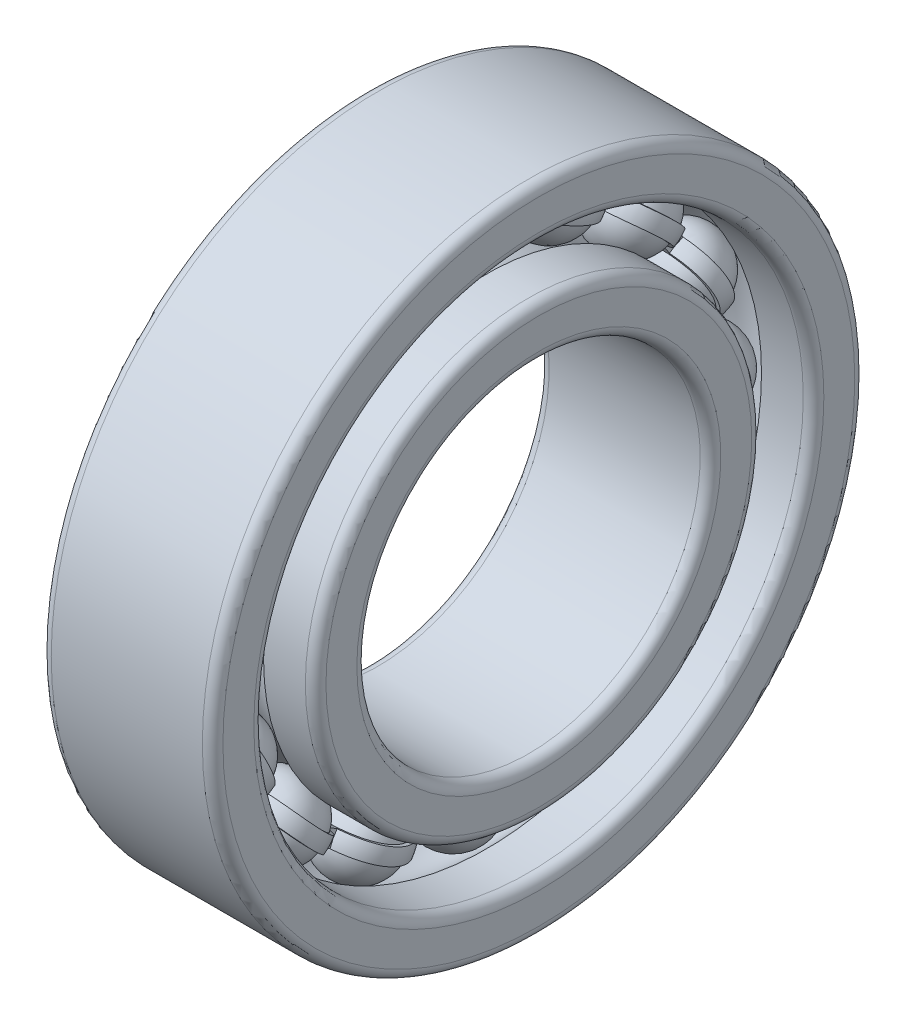
SolidWorks part; units mm, degrees
material "AISI 304"
ref_plane "前视基准面" through (0, 0, 0) normal (0, 0, 1) x (1, 0, 0)
ref_plane "上视基准面" through (0, 0, 0) normal (0, 1, 0) x (1, 0, 0)
ref_plane "右视基准面" through (0, 0, 0) normal (1, 0, 0) x (0, 0, -1)
sketch "尺寸草图" plane through (0, 0, 0) normal (0, 0, 1) x (1, 0, 0)
  line L0 (-19.9271, 0) -> (19.9271, 0) construction
  line L1 (0, 21.603) -> (0, -21.603) construction
  line L2 (-2.2, 9.5) -> (2.2, 9.5)
  line L3 (2.5, 9.2) -> (2.5, 8.3)
  line L4 (-2.5, 9.2) -> (-2.5, 8.3)
  line L5 (-2.2, 8) -> (2.2, 8)
  line L6 (-3.5, 7.25) -> (3.3577, 7.25) construction
  line L7 (-2.2, 6.5) -> (2.2, 6.5)
  line L8 (2.5, 6.2) -> (2.5, 5.3)
  line L9 (2.2, 5) -> (-2.2, 5)
  line L10 (-2.5, 5.3) -> (-2.5, 6.2)
  line L11 (0, 7.25) -> (0, 8.375) construction
  circle A0 centre (0, 7.25) radius 1.125
  arc A1 (2.5, 8.3) -> (2.2, 8) centre (2.2, 8.3) cw
  arc A2 (2.5, 6.2) -> (2.2, 6.5) centre (2.2, 6.2) ccw
  arc A3 (-2.2, 6.5) -> (-2.5, 6.2) centre (-2.2, 6.2) ccw
  arc A4 (-2.2, 8) -> (-2.5, 8.3) centre (-2.2, 8.3) cw
  arc A5 (-2.2, 5) -> (-2.5, 5.3) centre (-2.2, 5.3) cw
  arc A6 (2.2, 5) -> (2.5, 5.3) centre (2.2, 5.3) ccw
  arc A7 (2.5, 9.2) -> (2.2, 9.5) centre (2.2, 9.2) ccw
  arc A8 (-2.2, 9.5) -> (-2.5, 9.2) centre (-2.2, 9.2) ccw
  point P7 (0, 0)
  point P25 (-2.5, 6.5)
  point P28 (-2.5, 8)
  point P31 (-2.5, 5)
  point P36 (2.5, 9.5)
  point P39 (-2.5, 9.5)
  dimension "D1" = 0.375
  dimension "D3" = 0.3
  dimension "B" = 5
  dimension "D2" = 2.5
  dimension "D" = 19
  dimension "(d)" = 10
  dimension "D5" = 7.25
  dimension "D6" = 1.5
  dimension "D7" = 1.5
sketch "草图2" plane through (0, 0, 0) normal (0, 0, 1) x (1, 0, 0)
  line L6 (2.2, 5) -> (-2.2, 5) construction
  line L8 (-2.5, 9.2) -> (-2.5, 8.3) construction
  line L9 (-2.2, 8) -> (2.2, 8) construction
  line L10 (-2.2, 9.5) -> (2.2, 9.5) construction
  line L11 (2.5, 9.2) -> (2.5, 8.3) construction
  line L12 (2.5, 6.2) -> (2.5, 5.3) construction
  line L13 (-2.2, 6.5) -> (2.2, 6.5) construction
  line L14 (2.2, 5) -> (-2.2, 5)
  line L15 (-2.5, 5.3) -> (-2.5, 6.2) construction
  line L18 (-3.5, 0) -> (3.5, 0) construction
  line L19 (-19.9271, 0) -> (19.9271, 0) construction
  line L20 (-2.5, 9.2) -> (-2.5, 8.3)
  line L21 (-2.2, 8) -> (-0.8385, 8)
  line L22 (-2.2, 9.5) -> (2.2, 9.5)
  line L23 (2.5, 9.2) -> (2.5, 8.3)
  line L24 (2.5, 6.2) -> (2.5, 5.3)
  line L25 (-2.2, 6.5) -> (-0.8385, 6.5)
  line L26 (-2.5, 5.3) -> (-2.5, 6.2)
  line L27 (0.8385, 8) -> (2.2, 8)
  line L28 (0.8385, 6.5) -> (2.2, 6.5)
  circle A0 centre (0, 7.25) radius 1.125 construction
  arc A1 (0.8385, 8) -> (-0.8385, 8) centre (0, 7.25) ccw
  arc A2 (-0.8385, 6.5) -> (0.8385, 6.5) centre (0, 7.25) ccw
  arc A3 (-2.2, 9.5) -> (-2.5, 9.2) centre (-2.2, 9.2) ccw construction
  arc A4 (-2.5, 8.3) -> (-2.2, 8) centre (-2.2, 8.3) ccw construction
  arc A5 (2.5, 9.2) -> (2.2, 9.5) centre (2.2, 9.2) ccw construction
  arc A6 (2.2, 8) -> (2.5, 8.3) centre (2.2, 8.3) ccw construction
  arc A7 (2.5, 6.2) -> (2.2, 6.5) centre (2.2, 6.2) ccw construction
  arc A8 (2.2, 5) -> (2.5, 5.3) centre (2.2, 5.3) ccw construction
  arc A9 (-2.2, 6.5) -> (-2.5, 6.2) centre (-2.2, 6.2) ccw construction
  arc A10 (-2.5, 5.3) -> (-2.2, 5) centre (-2.2, 5.3) ccw construction
  arc A11 (-2.2, 9.5) -> (-2.5, 9.2) centre (-2.2, 9.2) ccw
  arc A12 (-2.5, 8.3) -> (-2.2, 8) centre (-2.2, 8.3) ccw
  arc A13 (2.5, 9.2) -> (2.2, 9.5) centre (2.2, 9.2) ccw
  arc A14 (2.2, 8) -> (2.5, 8.3) centre (2.2, 8.3) ccw
  arc A15 (2.5, 6.2) -> (2.2, 6.5) centre (2.2, 6.2) ccw
  arc A16 (2.2, 5) -> (2.5, 5.3) centre (2.2, 5.3) ccw
  arc A17 (-2.2, 6.5) -> (-2.5, 6.2) centre (-2.2, 6.2) ccw
  arc A18 (-2.5, 5.3) -> (-2.2, 5) centre (-2.2, 5.3) ccw
revolve "旋转1" add sketch "草图2" angle 360 about L18
sketch "草图5" plane through (0, 0, 0) normal (0, 0, 1) x (1, 0, 0)
  line L1 (-0.3375, 7.025) -> (0.3375, 7.025)
  line L2 (-0.3375, 7.025) -> (-0.3375, 7.475)
  line L3 (-0.3375, 7.475) -> (0.3375, 7.475)
  line L4 (0.3375, 7.025) -> (0.3375, 7.475)
  line L5 (-0.3375, 7.025) -> (0.3375, 7.475) construction
  line L6 (-0.3375, 7.475) -> (0.3375, 7.025) construction
  circle A0 centre (0, 7.25) radius 1.125 construction
  circle A1 centre (0, 7.25) radius 1.125 construction
  point P0 (0, 7.25)
  dimension "D1" = 0.675
  dimension "D2" = 0.45
revolve "旋转3" add sketch "草图5" angle 360 about L0
ref_axis "基准轴1" through (-3.85, 0, 0) along (1, 0, 0)
sketch "草图3" plane through (0, 0, 0) normal (0, 0, 1) x (1, 0, 0)
  line L1 (-1.2375, 7.25) -> (1.2375, 7.25)
  circle A0 centre (0, 7.25) radius 1.125 construction
  circle A1 centre (0, 7.25) radius 1.125 construction
  arc A2 (1.2375, 7.25) -> (-1.2375, 7.25) centre (0, 7.25) ccw
  dimension "D2" = 2.475
revolve "旋转2" add sketch "草图3" angle 360 about L1 region at (0, 7.7752, 0)
pattern_circular "阵列(圆周)5" count 16 over 360 about axis through (-3.85, 0, 0) along (1, 0, 0) of bodies 103
sketch "草图6" plane through (0, 0, 0) normal (0, 0, 1) x (1, 0, 0)
  line L0 (-1.2169, 7.475) -> (1.2169, 7.475)
  line L1 (-3.5, 7.25) -> (2.5, 7.25) construction
  line L3 (-1.2169, 7.025) -> (1.2169, 7.025)
  line L4 (2.5, -9.2) -> (2.5, 9.2) construction
  arc A0 (-1.2169, 7.025) -> (1.2169, 7.025) centre (0, 7.25) ccw
  circle A1 centre (0, 7.25) radius 1.125 construction
  circle A2 centre (0, 7.25) radius 1.125 construction
  arc A3 (1.2169, 7.475) -> (-1.2169, 7.475) centre (0, 7.25) ccw
  dimension "D1" = 2.475
  dimension "D3" = 0.225
  dimension "D4" = 0.225
revolve "切除-旋转1" cut sketch "草图6" angle 360 about L0
sketch "草图7" plane through (0, 0, 0) normal (0, 0, 1) x (1, 0, 0)
  line L0 (-1.125, 7.25) -> (1.125, 7.25)
  line L1 (-2.5, 0) -> (2.5, 0) construction
  line L2 (-2.5, 9.2) -> (-2.5, -9.2) construction
  line L3 (2.5, -9.2) -> (2.5, 9.2) construction
  circle A0 centre (0, 7.25) radius 1.125 construction
  arc A1 (1.125, 7.25) -> (-1.125, 7.25) centre (0, 7.25) ccw
revolve "旋转4" add sketch "草图7" angle 360 about L0
pattern_circular "阵列(圆周)2" count 16 over 360 about axis through (-3.85, 0, 0) along (1, 0, 0) of "旋转4"
